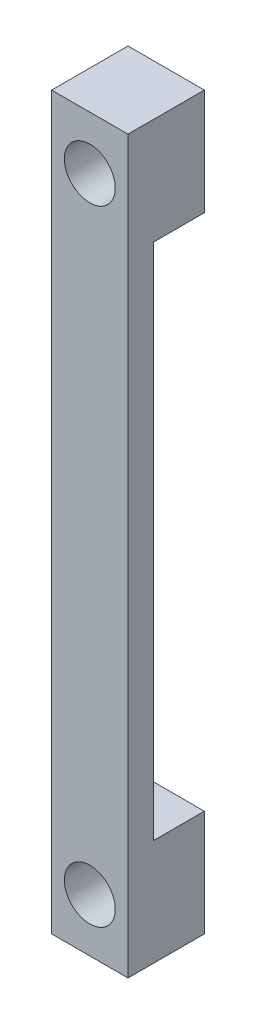
SolidWorks part; units mm, degrees
ref_plane "Front Plane" through (0, 0, 0) normal (0, 0, 1) x (1, 0, 0)
ref_plane "Top Plane" through (0, 0, 0) normal (0, 1, 0) x (1, 0, 0)
ref_plane "Right Plane" through (0, 0, 0) normal (1, 0, 0) x (0, 0, -1)
sketch "Sketch1" plane through (0, 0, 0) normal (0, 0, 1) x (1, 0, 0)
  line L1 (5.3028, 38.5661) -> (-3.6972, 38.5661)
  line L2 (5.3028, 38.5661) -> (5.3028, -47.5739)
  line L3 (5.3028, -47.5739) -> (-3.6972, -47.5739)
  line L4 (-3.6972, 38.5661) -> (-3.6972, -47.5739)
  line L5 (5.3028, 38.5661) -> (-3.6972, -47.5739) construction
  line L6 (5.3028, -47.5739) -> (-3.6972, 38.5661) construction
  circle A0 centre (0.8028, 32.3036) radius 2.5 construction
  point P0 (0, 0)
  point P10 (0, 0)
  dimension "D1" = 2
  dimension "D2" = 2
  dimension "D3" = 86.14
extrude "Boss-Extrude1" add sketch "Sketch1" along normal blind 3
sketch "Sketch2" plane through (0, 0, 0) normal (0, 0, -1) x (-1, 0, 0)
  line L0 (3.6972, 38.5661) -> (3.6972, -47.5739) construction
  line L1 (-5.3028, 38.5661) -> (3.6972, 38.5661)
  line L2 (-5.3028, 38.5661) -> (-5.3028, 26.0411)
  line L3 (-5.3028, 26.0411) -> (3.6972, 26.0411)
  line L4 (3.6972, 38.5661) -> (3.6972, 26.0411)
  line L5 (-12.8028, 26.0411) -> (67.2972, 26.0411) construction
  line L6 (-5.3028, -47.5739) -> (3.6972, -47.5739)
  line L7 (-5.3028, -47.5739) -> (-5.3028, -35.0489)
  line L8 (-5.3028, -35.0489) -> (3.6972, -35.0489)
  line L9 (3.6972, -47.5739) -> (3.6972, -35.0489)
  line L10 (-0.8028, 32.3036) -> (-0.8028, 38.5661)
  line L11 (-0.8028, -41.3114) -> (-0.8028, -47.5739)
  circle A0 centre (-0.8028, 32.3036) radius 3
  circle A1 centre (-0.8028, -41.3114) radius 3
  circle A3 centre (-0.8028, 32.3036) radius 2.5 construction
  line M9 (3.6972, -47.5739) -> (3.6972, 38.5661)
  line M11 (-5.3028, 38.5661) -> (-5.3028, -47.5739)
  line M12 (-5.3028, -47.5739) -> (3.6972, -47.5739)
  dimension "D1" = 6
extrude "Boss-Extrude2" add sketch "Sketch2" along normal blind 6 contours L8 A1 M11 M12 M9 | A0 | L2 L1 L4 L3 region at (-1.2585, 34.3649, 0) region at (0.8028, -35.2032, 0)
extrude "Cut-Extrude1" cut sketch "Sketch2<3>" against normal through all contours A0 | A1 | A1 region at (-1.2585, 34.3649, 0) region at (2.8641, -39.2501, 0)
sketch "Sketch2<3>" plane through (0, 0, 0) normal (0, 0, -1) x (-1, 0, 0) same geometry as "Sketch2"
equation "\"D2@Sketch1\"=\"D1@Sketch1\""
